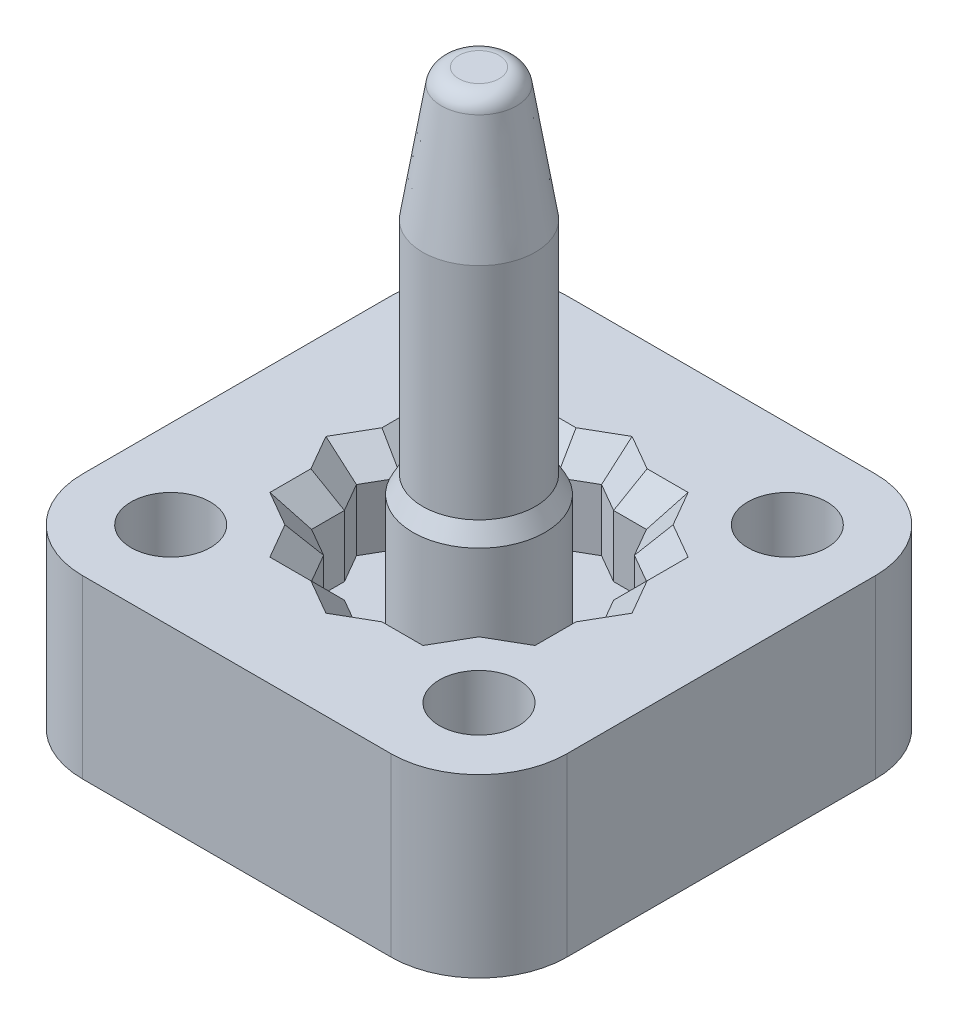
SolidWorks part; units mm, degrees
ref_plane "Front Plane" through (0, 0, 0) normal (0, 0, 1) x (1, 0, 0)
ref_plane "Top Plane" through (0, 0, 0) normal (0, 1, 0) x (1, 0, 0)
ref_plane "Right Plane" through (0, 0, 0) normal (1, 0, 0) x (0, 0, -1)
sketch "Sketch1" plane through (0, 0, 0) normal (0, 0, 1) x (1, 0, 0)
  line L0 (0, 27.5) -> (0, -27.5) construction
  line L1 (0, 27.5) -> (2.2946, 27.5)
  line L2 (4.2694, 25.816) -> (6.4, 12.5)
  line L3 (6.4, 12.5) -> (6.4, -12.5)
  line L4 (6.4, -27.5) -> (0, -27.5)
  line L5 (0, 27.5) -> (0, -27.5)
  line L6 (6.4, -12.5) -> (7.5, -12.5)
  line L7 (7.5, -12.5) -> (7.5, -27.5)
  line L8 (7.5, -27.5) -> (6.4, -27.5)
  arc A0 (2.2946, 27.5) -> (4.2694, 25.816) centre (2.2946, 25.5) cw
  point P4 (0, 0)
  point P10 (4, 27.5)
  dimension "D5" = 2
  dimension "D1" = 40
  dimension "D2" = 15
  dimension "D3" = 12.8
  dimension "D4" = 4
  dimension "D6" = 7.5
  dimension "D7" = 15
revolve "Revolve1" add sketch "Sketch1" angle 360 about L0
sketch "Sketch2" plane through (0, -27.5, 0) normal (0, -1, 0) x (1, 0, 0)
  line L0 (27.5, 27.5) -> (-27.5, -27.5) construction
  line L1 (17.5, 27.5) -> (-17.5, 27.5)
  line L2 (27.5, 17.5) -> (27.5, -17.5)
  line L3 (17.5, -27.5) -> (-17.5, -27.5)
  line L4 (-27.5, 17.5) -> (-27.5, -17.5)
  arc A0 (-17.5, 27.5) -> (-27.5, 17.5) centre (-17.5, 17.5) ccw
  arc A1 (-17.5, -27.5) -> (-27.5, -17.5) centre (-17.5, -17.5) cw
  arc A2 (27.5, -17.5) -> (17.5, -27.5) centre (17.5, -17.5) cw
  arc A3 (17.5, 27.5) -> (27.5, 17.5) centre (17.5, 17.5) cw
  dimension "D2" = 10
  dimension "D1" = 55
extrude "Boss-Extrude1" add sketch "Sketch2" along normal blind 10
sketch "Sketch3" plane through (0, -27.5, 0) normal (0, 1, 0) x (1, 0, 0)
  circle A0 centre (-17.5, 17.5) radius 4.5
  dimension "D1" = 9
extrude "Cut-Extrude1" cut sketch "Sketch3" against normal through all
mirror "Mirror1" about plane through (0, 0, 0) normal (0, 0, 1) of "Cut-Extrude1" second plane through (0, 0, 0) second plane normal (1, 0, 0)
sketch "Sketch4" plane through (0, -27.5, 0) normal (0, 1, 0) x (1, 0, 0)
  line L0 (17.5, -27.5) -> (-17.5, -27.5) construction
  line L1 (-17.5, 27.5) -> (17.5, 27.5)
  line L2 (-27.5, 17.5) -> (-27.5, -17.5)
  line L3 (-17.5, -27.5) -> (17.5, -27.5)
  line L4 (27.5, 17.5) -> (27.5, -17.5)
  line L5 (27.5, 17.5) -> (27.5, -17.5) construction
  line L6 (-17.5, 27.5) -> (17.5, 27.5) construction
  line L7 (-27.5, -17.5) -> (-27.5, 17.5) construction
  line L8 (-12.05, 3.2288) -> (-13.9141, 0)
  line L9 (13.9141, 0) -> (12.05, 3.2288)
  line L10 (6.9571, 12.05) -> (3.2288, 12.05)
  line L11 (-6.9571, 12.05) -> (-8.8212, 8.8212)
  line L12 (-13.9141, 0) -> (-12.05, -3.2288)
  line L13 (-6.9571, -12.05) -> (-3.2288, -12.05)
  line L14 (6.9571, -12.05) -> (8.8212, -8.8212)
  line L15 (-12.05, 6.9571) -> (-12.05, 3.2288)
  line L16 (-12.05, -6.9571) -> (-8.8212, -8.8212)
  line L17 (0, -13.9141) -> (3.2288, -12.05)
  line L18 (12.05, -6.9571) -> (12.05, -3.2288)
  line L19 (12.05, 6.9571) -> (8.8212, 8.8212)
  line L20 (0, 13.9141) -> (-3.2288, 12.05)
  line L21 (-8.8212, 8.8212) -> (-12.05, 6.9571)
  line L22 (-12.05, -3.2288) -> (-12.05, -6.9571)
  line L23 (-8.8212, -8.8212) -> (-6.9571, -12.05)
  line L24 (-3.2288, -12.05) -> (0, -13.9141)
  line L25 (8.8212, -8.8212) -> (12.05, -6.9571)
  line L26 (12.05, -3.2288) -> (13.9141, 0)
  line L27 (12.05, 3.2288) -> (12.05, 6.9571)
  line L28 (8.8212, 8.8212) -> (6.9571, 12.05)
  line L29 (3.2288, 12.05) -> (0, 13.9141)
  line L30 (-3.2288, 12.05) -> (-6.9571, 12.05)
  line L31 (3.2288, -12.05) -> (6.9571, -12.05)
  arc A0 (17.5, 27.5) -> (27.5, 17.5) centre (17.5, 17.5) cw
  arc A1 (17.5, -27.5) -> (27.5, -17.5) centre (17.5, -17.5) ccw
  arc A2 (-27.5, -17.5) -> (-17.5, -27.5) centre (-17.5, -17.5) ccw
  arc A3 (-17.5, 27.5) -> (-27.5, 17.5) centre (-17.5, 17.5) ccw
  circle A5 centre (-17.5, 17.5) radius 4.5
  circle A6 centre (17.5, 17.5) radius 4.5
  circle A7 centre (17.5, -17.5) radius 4.5
  circle A8 centre (-17.5, -17.5) radius 4.5
  circle A9 centre (0, 0) radius 12.4751 construction
  circle A10 centre (0, 0) radius 13.9141 construction
  point P29 (0, 0)
  point P51 (0, 0)
  dimension "D1" = 10
  dimension "D3" = 9
  dimension "D4" = 24.9502
  dimension "D2" = 24.1
extrude "Boss-Extrude2" add sketch "Sketch4" along normal blind 10
chamfer "Chamfer1" distance 3 angle 45 24 edges at (-12.9821, -17.5, 1.6144) (-5.0929, -17.5, 12.05) (7.8891, -17.5, 10.4356) (12.9821, -17.5, -1.6144) (5.0929, -17.5, -12.05) (-7.8891, -17.5, -10.4356) (-12.9821, -17.5, -1.6144) (-12.05, -17.5, -5.0929) (-10.4356, -17.5, -7.8891) (-12.05, -17.5, 5.0929) (-10.4356, -17.5, 7.8891) (-7.8891, -17.5, 10.4356) (-1.6144, -17.5, 12.9821) (1.6144, -17.5, 12.9821) (5.0929, -17.5, 12.05) (10.4356, -17.5, 7.8891) (12.05, -17.5, 5.0929) (12.9821, -17.5, 1.6144) (12.05, -17.5, -5.0929) (10.4356, -17.5, -7.8891) (7.8891, -17.5, -10.4356) (1.6144, -17.5, -12.9821) (-1.6144, -17.5, -12.9821) (-5.0929, -17.5, -12.05)
chamfer "Chamfer2" distance 2 distance2 1.1 1 edges at (0, -12.5, 7.5) first distance on face at (0, -12.5, 7.5)
